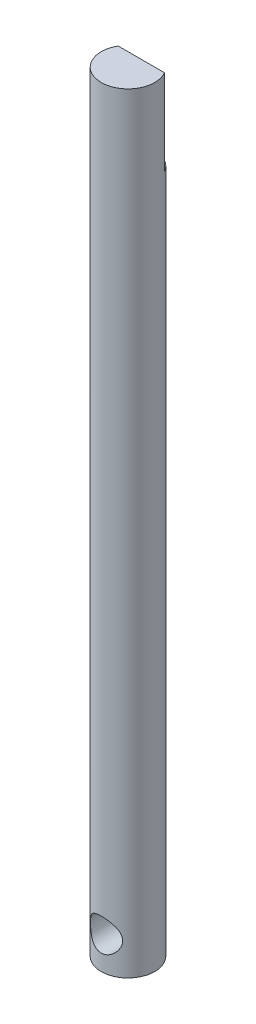
SolidWorks part; units mm, degrees
material "Plain Carbon Steel"
ref_plane "Front Plane" through (0, 0, 0) normal (0, 0, 1) x (1, 0, 0)
ref_plane "Top Plane" through (0, 0, 0) normal (0, 1, 0) x (1, 0, 0)
ref_plane "Right Plane" through (0, 0, 0) normal (1, 0, 0) x (0, 0, -1)
sketch "Sketch1" plane through (0, 0, 0) normal (0, 1, 0) x (1, 0, 0)
  circle A0 centre (0, 0) radius 3.9688
extrude "Boss-Extrude1" add sketch "Sketch1" along normal blind 114.3
sketch "Sketch2" plane through (0, 114.3, 0) normal (0, 1, 0) x (1, 0, 0)
  line L0 (0, 0) -> (3.437, 1.9844) construction
  line L1 (3.437, 1.9844) -> (-3.437, 1.9844)
  line L2 (-3.437, 1.9844) -> (0, 0) construction
  line L3 (-3.437, 1.9844) -> (-4.7194, 2.5225)
  line L4 (-4.7194, 2.5225) -> (-2.5902, 6.3532)
  line L5 (-2.5902, 6.3532) -> (2.4567, 4.7289)
  line L6 (2.4567, 4.7289) -> (3.437, 1.9844)
  circle A1 centre (0, 0) radius 3.9688 construction
  point P2 (0, 1.9844)
  dimension "D1" = 120
extrude "Cut-Extrude1" cut sketch "Sketch2" against normal blind 12.7
sketch "Sketch3" plane through (0, 0, -1.9844) normal (0, 0, -1) x (-1, 0, 0)
  line L0 (0, 0) -> (0, 9.525) construction
  circle A0 centre (0, 4.7625) radius 2.3813
  dimension "D2" = 4.7625
  dimension "D1" = 9.525
extrude "Cut-Extrude2" cut sketch "Sketch3" against normal blind 12.7 and the other way blind 12.7
